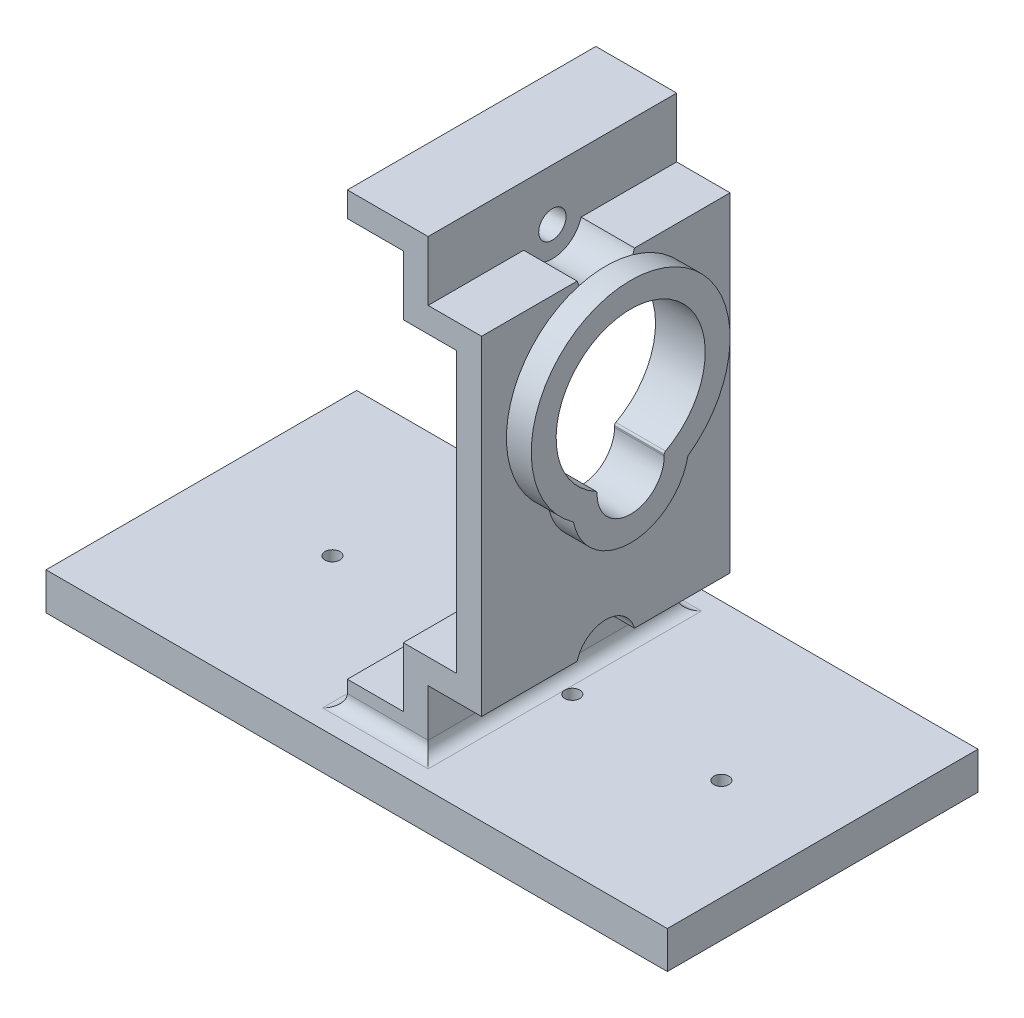
SolidWorks part; units mm, degrees
ref_plane "Ön Düzlem" through (0, 0, 0) normal (0, 0, 1) x (1, 0, 0)
ref_plane "Üst Düzlem" through (0, 0, 0) normal (0, 1, 0) x (1, 0, 0)
ref_plane "Sağ Düzlem" through (0, 0, 0) normal (1, 0, 0) x (0, 0, -1)
sketch "Çizim1" plane through (0, 0, 0) normal (0, 1, 0) x (1, 0, 0)
  line L8 (-1.9, 6.45) -> (-1.9, 2.8797)
  line L9 (-25, -12.5) -> (25, -12.5)
  line L10 (-25, -12.5) -> (-25, 12.5)
  line L11 (-25, 12.5) -> (25, 12.5)
  line L12 (25, -12.5) -> (25, 12.5)
  line L13 (-25, -12.5) -> (25, 12.5) construction
  line L14 (-25, 12.5) -> (25, -12.5) construction
  line L15 (-2.2091, 2.65) -> (-14.1591, 1.997)
  line L16 (-14.1591, -1.997) -> (-2.2091, -2.65)
  line L17 (-1.9, -2.8797) -> (-1.9, -6.45)
  line L18 (1.9, -6.45) -> (1.9, -3.2953)
  line L19 (1.9, -3.2953) -> (16.6263, -1.9922)
  line L20 (16.6263, 1.9922) -> (1.9, 3.2953)
  line L21 (1.9, 3.2953) -> (1.9, 6.45)
  line L22 (-14.45, 0) -> (16.85, 0) construction
  line L23 (0, 6.45) -> (0, -6.45) construction
  arc A7 (-1.9, 2.8797) -> (-2.2091, 2.65) centre (0, 0) ccw
  arc A8 (-14.1591, 1.997) -> (-14.1591, -1.997) centre (-14.05, 0) ccw
  arc A9 (-2.2091, -2.65) -> (-1.9, -2.8797) centre (0, 0) ccw
  arc A10 (-1.9, -6.45) -> (1.9, -6.45) centre (0, -6.45) ccw
  arc A11 (16.6263, -1.9922) -> (16.6263, 1.9922) centre (16.45, 0) ccw
  arc A12 (1.9, 6.45) -> (-1.9, 6.45) centre (0, 6.45) ccw
  circle A13 centre (-14.45, 0) radius 0.6
  circle A14 centre (4.85, 0) radius 0.6
  circle A15 centre (-4.45, 0) radius 0.6
  circle A16 centre (16.85, 0) radius 0.6
  circle A17 centre (0, 6.45) radius 0.6
  circle A18 centre (0, -6.45) radius 0.6
  dimension "D1" = 50
  dimension "D2" = 25
extrude "Yükseklik-Ekstrüzyon3" add sketch "Çizim1" along normal blind 1.5 contours L9 L12 L11 L10 A12 L21 L20 A11 L19 L18 A10 L17 A9 L16 A8 L15 A7 L8 region at (-24.441, 0, 0)
sketch "Çizim6" plane through (0, 1.5, 0) normal (0, 1, 0) x (1, 0, 0)
  line L4 (-25, -12.5) -> (25, -12.5)
  line L5 (25, -12.5) -> (25, 12.5)
  line L6 (25, 12.5) -> (-25, 12.5)
  line L7 (-25, 12.5) -> (-25, -12.5)
  line L8 (-25, -12.5) -> (25, -12.5)
  line L9 (25, -12.5) -> (25, 12.5)
  line L10 (25, 12.5) -> (-25, 12.5)
  line L11 (-25, 12.5) -> (-25, -12.5)
  dimension "D1" = 0
extrude "Yükseklik-Ekstrüzyon4" add sketch "Çizim6" along normal blind 1.5
extrude "Kes-Ekstrüzyon1" cut sketch "Çizim1<5>" along normal blind 3 contours A13 | A15 | A18 | A14 | A16 | A17
sketch "Çizim1<5>" plane through (0, 0, 0) normal (0, 1, 0) x (1, 0, 0) same geometry as "Çizim1"
ref_plane "Düzlem1" through (0, 0, 0) normal (0, 0, -1) x (-1, 0, 0)
sketch "Çizim7" plane through (0, 0, 0) normal (0, 0, -1) x (-1, 0, 0)
  line L0 (-25, 3) -> (25, 3) construction
  line L7 (-1.25, 8.8) -> (-1.25, 5)
  line L8 (3.25, 3) -> (3.25, 5)
  line L9 (-1.25, 5) -> (1.25, 5)
  line L11 (-1.25, 37.1) -> (1.25, 37.1)
  line L13 (-5.55, 9.8) -> (-5.5503, 32.2998)
  line L14 (-1.25, 33.2998) -> (-1.25, 37.1)
  line L15 (-3.25, 3) -> (3.25, 3)
  line L16 (-3.25, 7.8) -> (-3.25, 3)
  line L17 (-3.25, 7.8) -> (-7.55, 7.8)
  line L18 (-7.55, 7.8) -> (-7.5503, 34.2997)
  line L19 (-7.5503, 34.2997) -> (-3.25, 34.2999)
  line L20 (-3.25, 34.2999) -> (-3.25, 39.1)
  line L21 (-3.25, 39.1) -> (3.25, 39.1)
  line L22 (3.25, 39.1) -> (3.25, 37.1)
  line L23 (-5.5503, 32.2998) -> (-1.25, 32.2998)
  line L24 (-1.25, 32.2998) -> (-1.25, 33.2998)
  line L28 (-5.55, 9.8) -> (-1.25, 9.8)
  line L29 (-1.25, 9.8) -> (-1.25, 8.8)
  line L33 (1.25, 37.1) -> (3.25, 37.1)
  line L34 (1.25, 5) -> (3.25, 5)
  point P0 (0, 3)
extrude "Yükseklik-Ekstrüzyon5" add sketch "Çizim7" along normal mid plane 20
fillet "Radyus1" radius 1 4 edges at (3.25, 3, 0) (0, 3, 10) (-3.25, 3, 0) (0, 3, -10)
sketch "Çizim8" plane through (7.5499, -0.0001, 0) normal (1, 0, 0) x (0, 0, -1)
  line L0 (-2.7, 20.7201) -> (-2.7, 20.6)
  line L1 (0, 39.1) -> (0, 26.2) construction
  line L2 (2.7, 20.6) -> (2.7, 20.7201)
  arc A0 (-2.7, 20.6) -> (2.7, 20.6) centre (0, 20.6) ccw
  arc A1 (2.8065, 20.8969) -> (2.7, 20.7201) centre (2.9, 20.7201) ccw
  arc A2 (2.8065, 20.8969) -> (-2.8065, 20.8969) centre (0, 26.2) ccw
  arc A3 (-2.7, 20.7201) -> (-2.8065, 20.8969) centre (-2.9, 20.7201) ccw
  arc A4 (-4.6046, 19.6581) -> (4.6046, 19.6581) centre (0, 20.6) ccw
  arc A5 (4.6046, 19.6581) -> (-4.6046, 19.6581) centre (0, 26.2) ccw
extrude "Yükseklik-Ekstrüzyon6" add sketch "Çizim8" along normal blind 2
sketch "Çizim9" plane through (7.5499, -0.0001, 0) normal (1, 0, 0) x (0, 0, -1)
  line L2 (-2.7, 20.7201) -> (-2.7, 20.6)
  line L3 (2.7, 20.6) -> (2.7, 20.7201)
  line L4 (-2.7, 20.7201) -> (-2.7, 20.6)
  line L5 (2.7, 20.6) -> (2.7, 20.7201)
  arc A4 (2.8065, 20.8969) -> (-2.8065, 20.8969) centre (0, 26.2) ccw
  arc A5 (-2.7, 20.7201) -> (-2.8065, 20.8969) centre (-2.9, 20.7201) ccw
  arc A6 (-2.7, 20.6) -> (2.7, 20.6) centre (0, 20.6) ccw
  arc A7 (2.8065, 20.8969) -> (2.7, 20.7201) centre (2.9, 20.7201) ccw
  arc A8 (2.8065, 20.8969) -> (-2.8065, 20.8969) centre (0, 26.2) ccw
  arc A9 (-2.7, 20.7201) -> (-2.8065, 20.8969) centre (-2.9, 20.7201) ccw
  arc A10 (-2.7, 20.6) -> (2.7, 20.6) centre (0, 20.6) ccw
  arc A11 (2.8065, 20.8969) -> (2.7, 20.7201) centre (2.9, 20.7201) ccw
  dimension "D1" = 0
extrude "Kes-Ekstrüzyon2" cut sketch "Çizim9" against normal blind 2
sketch "Çizim10" plane through (3.25, 0, 0) normal (1, 0, 0) x (0, 0, -1)
  line L0 (0, 7.15) -> (0, 3) construction
  circle A0 centre (0, 7.15) radius 1.1
  dimension "D1" = 2.2
extrude "Kes-Ekstrüzyon3" cut sketch "Çizim10" against normal blind 5 and the other way blind 9
sketch "Çizim11" plane through (3.25, 0, 0) normal (1, 0, 0) x (0, 0, -1)
  circle A0 centre (0, 7.15) radius 2.4
  point P2 (0, 7.15)
extrude "Kes-Ekstrüzyon4" cut sketch "Çizim11" along normal blind 9
ref_plane "Düzlem3" through (0, 21.05, 0) normal (0, -1, 0) x (-1, 0, 0)
mirror "Aynalama1" about plane through (0, 21.05, 0) normal (0, -1, 0) of "Kes-Ekstrüzyon3", "Kes-Ekstrüzyon4"
sketch "Çizim12" plane through (9.5499, -0.0001, 0) normal (1, 0, 0) x (0, 0, -1)
  line L0 (5.1293, 32.3393) -> (-5.1293, 32.3393)
  arc A0 (5.1293, 32.3393) -> (-5.1293, 32.3393) centre (0, 26.2) ccw
extrude "Yükseklik-Ekstrüzyon7" add sketch "Çizim12" against normal up to surface (2 mm away) up to face at (7.5502, 22.921, 0)
